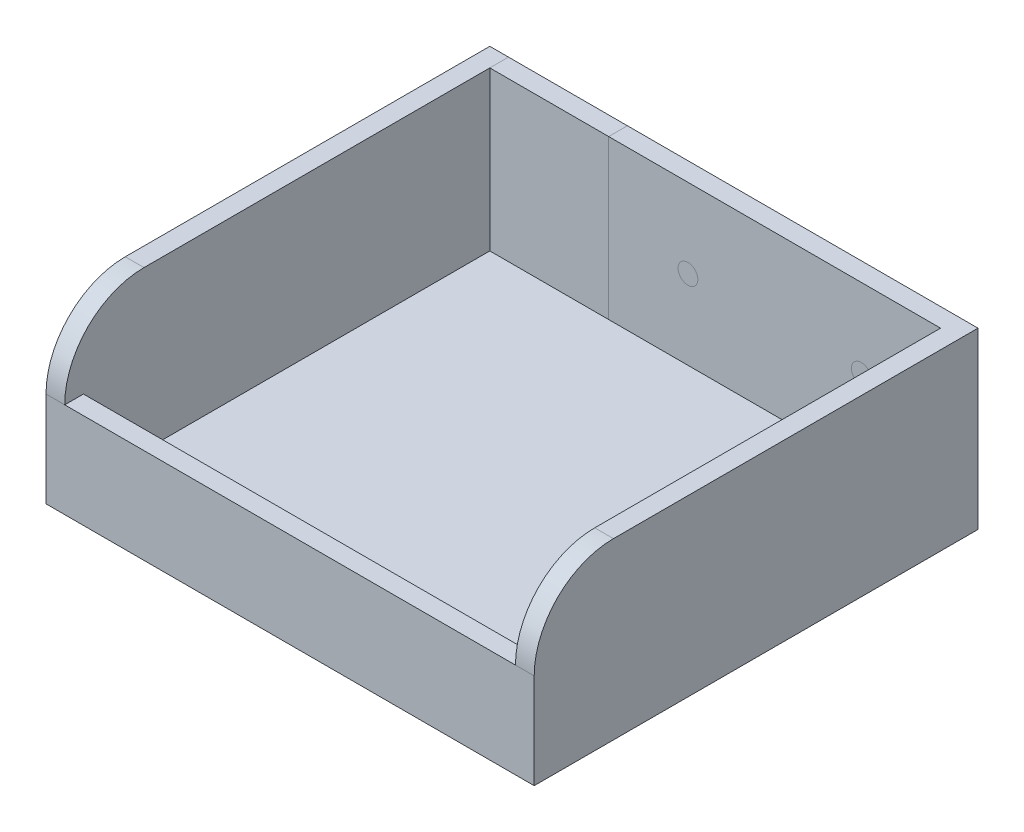
SolidWorks part; units mm, degrees
note: The reader was unsure of these and kept them because the rebuilt part matched: shared geometry of "Sketch1<3>", "Sketch1<4>", "Sketch3<2>".
material "ABS"
ref_plane "Front Plane" through (0, 0, 0) normal (0, 0, 1) x (1, 0, 0)
ref_plane "Top Plane" through (0, 0, 0) normal (0, 1, 0) x (1, 0, 0)
ref_plane "Right Plane" through (0, 0, 0) normal (1, 0, 0) x (0, 0, -1)
sketch "Sketch1" plane through (0, 0, 0) normal (0, 1, 0) x (1, 0, 0)
  line L0 (-36.116, 32.56) -> (-36.116, -32.56)
  line L1 (-39.116, 35.56) -> (39.116, 35.56)
  line L2 (-39.116, 35.56) -> (-39.116, -35.56)
  line L3 (-39.116, -35.56) -> (39.116, -35.56)
  line L4 (39.116, 35.56) -> (39.116, -35.56)
  line L5 (-39.116, 35.56) -> (39.116, -35.56) construction
  line L6 (-39.116, -35.56) -> (39.116, 35.56) construction
  line L7 (-36.116, -32.56) -> (36.116, -32.56)
  line L8 (36.116, 32.56) -> (36.116, -32.56)
  line L9 (-36.116, 32.56) -> (36.116, 32.56)
  line L10 (-36.116, 32.56) -> (-36.116, 35.56)
  line L11 (-17.066, 32.56) -> (-17.066, 35.56)
  point P0 (0, 0)
  dimension "D1" = 78.232
  dimension "D2" = 71.12
  dimension "D4" = 19.05
  dimension "D3" = 3
extrude "Boss-Extrude1" add sketch "Sketch1" along normal blind 2.54 contours L0 L7 L8 L9
extrude "Boss-Extrude2" add sketch "Sketch1<3>" along normal blind 27.94 contours L11 L9 L8 L7 L0 L10 L1 L2 L3 L4
sketch "Sketch1<3>" plane through (0, 0, 0) normal (0, 1, 0) x (1, 0, 0) same geometry as "Sketch1"
extrude "Boss-Extrude3" add sketch "Sketch1<4>" along normal blind 27.94 separate body contours L9 L11 L1 L10
sketch "Sketch1<4>" plane through (0, 0, 0) normal (0, 1, 0) x (1, 0, 0) same geometry as "Sketch1"
sketch "Sketch2" plane through (0, 0, 35.56) normal (0, 0, 1) x (1, 0, 0)
  line L0 (-36.116, 15.24) -> (36.116, 15.24)
  line L4 (-36.116, 2.54) -> (36.116, 2.54)
  line L5 (-36.116, 27.94) -> (-36.116, 2.54)
  line L6 (36.116, 27.94) -> (-36.116, 27.94)
  line L7 (36.116, 2.54) -> (36.116, 27.94)
  line L8 (-36.116, 2.54) -> (36.116, 2.54)
  line L9 (-36.116, 27.94) -> (-36.116, 2.54)
  line L10 (36.116, 27.94) -> (-36.116, 27.94)
  line L11 (36.116, 2.54) -> (36.116, 27.94)
  line M8 (39.116, 27.94) -> (-39.116, 27.94)
  dimension "D2" = 12.7
  dimension "D1" = 0
extrude "Cut-Extrude1" cut sketch "Sketch2" against normal blind 27.94 contours L0 L11 L9 M8
fillet "Fillet1" radius 12.7 2 edges at (-37.616, 27.94, 35.56) (37.616, 27.94, 35.56)
sketch "Sketch3" plane through (0, 0, -32.56) normal (0, 0, 1) x (1, 0, 0)
  line L0 (-17.066, 15.24) -> (36.116, 15.24) construction
  line L4 (-17.066, 27.94) -> (-17.066, 2.54)
  line L5 (-17.066, 2.54) -> (36.116, 2.54)
  line L6 (36.116, 2.54) -> (36.116, 27.94)
  line L7 (36.116, 27.94) -> (-17.066, 27.94)
  line L8 (-17.066, 27.94) -> (-17.066, 2.54) construction
  line L9 (-17.066, 2.54) -> (36.116, 2.54) construction
  line L10 (36.116, 2.54) -> (36.116, 27.94) construction
  line L11 (36.116, 27.94) -> (-17.066, 27.94) construction
  circle A0 centre (23.416, 15.24) radius 1.5875
  circle A1 centre (-4.366, 15.24) radius 1.5875
  dimension "D2" = 3.175
  dimension "D3" = 3.175
  dimension "D4" = 12.7
  dimension "D5" = 12.7
  dimension "D1" = 0
extrude "Cut-Extrude2" cut sketch "Sketch3" against normal blind 3
extrude "Boss-Extrude4" add sketch "Sketch3<2>" against normal blind 3 separate body
sketch "Sketch3<2>" plane through (0, 0, -32.56) normal (0, 0, 1) x (1, 0, 0) same geometry as "Sketch3"
